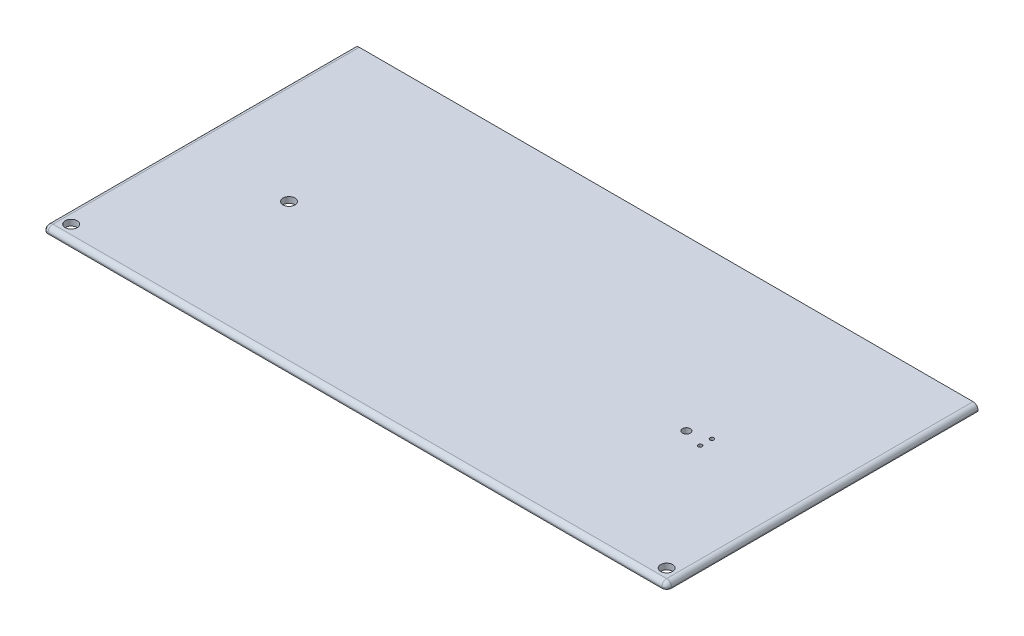
SolidWorks part; units mm, degrees
ref_plane "Front Plane" through (0, 0, 0) normal (0, 0, 1) x (1, 0, 0)
ref_plane "Top Plane" through (0, 0, 0) normal (0, 1, 0) x (1, 0, 0)
ref_plane "Right Plane" through (0, 0, 0) normal (1, 0, 0) x (0, 0, -1)
sketch "Sketch1" plane through (0, 0, 0) normal (0, 1, 0) x (1, 0, 0)
  line L0 (79.25, -36) -> (79.25, 36)
  line L1 (-78, -34.75) -> (78, -34.75)
  line L2 (-78, -34.75) -> (-78, 34.75)
  line L3 (-78, 34.75) -> (78, 34.75)
  line L4 (78, -34.75) -> (78, 34.75)
  line L5 (-78, -34.75) -> (78, 34.75) construction
  line L6 (-78, 34.75) -> (78, -34.75) construction
  line L7 (-79.25, 36) -> (79.25, 36)
  line L8 (-79.25, -36) -> (-79.25, 36)
  line L9 (-78, -36) -> (78, -36)
  line L10 (-78, -36) -> (-78, -86)
  line L11 (-78, -36) -> (78, -36)
  line L12 (-79.25, -36) -> (-79.25, -86)
  line L13 (-79.25, -86) -> (-79.25, -159)
  line L14 (79.25, -36) -> (79.25, -86)
  line L15 (78, -36) -> (78, -86)
  line L16 (-79.25, -36) -> (79.25, -36) construction
  line L17 (-78, -86) -> (-78, -100.5886)
  line L18 (79.25, -86) -> (79.25, -159)
  line L19 (78, -86) -> (78, -157.75)
  line L20 (79.25, -159) -> (-79.25, -159)
  line L21 (78, -159) -> (79.25, -159)
  line L22 (-78, -100.5886) -> (-78, -157.75)
  line L23 (-78, -157.75) -> (78, -157.75)
  line L24 (-78, -157.75) -> (78, -157.75) construction
  line L25 (0, -157.75) -> (0, -117.25)
  line L26 (-40, -117.25) -> (40, -117.25)
  line L27 (-34, -117.25) -> (34, -117.25)
  line L28 (-40, -117.25) -> (-34, -117.25) construction
  circle A0 centre (-37, -117.25) radius 3
  point P0 (0, 0)
  point P27 (0, -117.25)
  point P30 (0, -117.25)
  dimension "D1" = 156
  dimension "D2" = 69.5
  dimension "D4" = 50
  dimension "D5" = 195
  dimension "D6" = 1.25
  dimension "D7" = 40.5
  dimension "D8" = 80
  dimension "D9" = 68
  dimension "D3" = 1.25
sketch "Sketch2" plane through (0, 0, 0) normal (0, 1, 0) x (1, 0, 0)
  line L0 (-79.25, 36) -> (79.25, 36)
  line L1 (79.25, 36) -> (79.25, -159)
  line L2 (79.25, -159) -> (-79.25, -159)
  line L3 (-79.25, -159) -> (-79.25, 36)
extrude "Boss-Extrude1" add sketch "Sketch2" against normal blind 1.25
extrude "Boss-Extrude2" add sketch "Sketch1" along normal blind 105 contours L20 L18 L14 L0 L7 L8 L12 L13 L23 L22 L17 L10 L9 L15 L19 L4 L1 L2 L3 region at (78.9987, 0, 61)
sketch "Sketch4" plane through (0, 0, 0) normal (0, 1, 0) x (1, 0, 0)
  line L0 (-78, -157.75) -> (78, -157.75) construction
  line L1 (0, -157.75) -> (0, -117.75)
  line L2 (0, -5.0875) -> (0, 5.0875) construction
  line L3 (-34, -117.75) -> (34, -117.75)
  line L4 (-40.15, -117.75) -> (-39.575, -117.75)
  line L5 (-40.15, -117.75) -> (-39.575, -117.75) construction
  line L6 (34, -117.75) -> (34.575, -117.75) construction
  line L7 (-34.575, -117.75) -> (34.575, -117.75)
  line L8 (-34.575, -117.75) -> (-34, -117.75) construction
  line L9 (39.575, -117.75) -> (40.15, -117.75) construction
  line L10 (39.575, -117.75) -> (40.15, -117.75)
  circle A0 centre (-37.075, -117.75) radius 2.5
  circle A1 centre (37.075, -117.75) radius 2.5
  point P12 (0, -117.75)
  point P15 (0, -117.75)
  dimension "D1" = 40
  dimension "D2" = 68
  dimension "D3" = 80.3
extrude "Boss-Extrude3" add sketch "Sketch4" along normal blind 8 contours A0 | A1 region at (37.075, 0, 117.75) region at (-37.075, 0, 117.75)
fillet "Fillet2" radius 2 18 edges at (-78, 0, 0) (0, 0, -34.75) (78, 0, 0) (0, 0, 34.75) (0, 0, 36) (78, 0, 96.875) (0, 0, 157.75) (-78, 0, 96.875) (-37.075, 0, 115.25) (37.075, 0, 115.25) (78, 52.5, -34.75) (-78, 52.5, -34.75) (78, 52.5, 34.75) (-78, 52.5, 34.75) (-78, 52.5, 157.75) (78, 52.5, 157.75) (78, 52.5, 36) (-78, 52.5, 36)
sketch "Sketch5" plane through (0, 0, 36) normal (0, 0, 1) x (1, 0, 0)
  line L0 (-76, 105) -> (76, 105) construction
  line L2 (-76, 105) -> (-76, 2) construction
  line L3 (-58.75, 4.5) -> (58.75, 4.5)
  line L4 (-58.75, 4.5) -> (-58.75, 101.5)
  line L5 (-58.75, 101.5) -> (58.75, 101.5)
  line L6 (58.75, 4.5) -> (58.75, 101.5)
  line L7 (-58.75, 53) -> (58.75, 53)
  line L8 (-53.75, 101.5) -> (-53.75, 98)
  line L14 (-58.75, 98) -> (-53.75, 98)
  line L15 (0, 53) -> (0, 77.907)
  circle A0 centre (-53.75, 98) radius 1.55
  circle A1 centre (-53.75, 8) radius 1.55
  circle A2 centre (53.75, 8) radius 1.55
  circle A3 centre (53.75, 98) radius 1.55
  point P8 (0, 53.5)
  dimension "D1" = 97
  dimension "D2" = 117.5
  dimension "D3" = 17.25
  dimension "D4" = 3.5
  dimension "D5" = 5
  dimension "D6" = 3.5
extrude "Cut-Extrude1" cut sketch "Sketch5" against normal blind 8 contours L14 A0 L8 | L8 A0 L14 | A3 | A1 | A2 region at (-54.4078, 98.6578, 36) region at (-53.5307, 97.7807, 36) region at (-53.75, 8, 36) region at (53.75, 98, 36)
sketch "Sketch6" plane through (0, 0, 157.75) normal (0, 0, -1) x (-1, 0, 0)
  line L0 (-76, 2) -> (76, 2) construction
  line L1 (0, 2) -> (0, 22)
  line L2 (0, 5.0875) -> (0, -5.0875) construction
  circle A0 centre (0, 22) radius 8.25
  dimension "D1" = 20
extrude "Cut-Extrude2" cut sketch "Sketch6" against normal blind 8 contours A0 region at (-5.6686, 16.3314, 157.75)
sketch "Sketch8" plane through (-79.25, 0, 0) normal (-1, 0, 0) x (0, 0, 1)
  line L0 (159, 55) -> (116.5, 55)
  line L1 (159, -1.25) -> (159, 105) construction
  line L2 (116.5, 5) -> (116.5, 105)
  line L3 (159, 105) -> (-36, 105) construction
  line L4 (116.5, 55) -> (101.5, 55)
  line L5 (116.5, 55) -> (131.5, 55)
  line L7 (113, 58) -> (120, 58)
  line L8 (113, 58) -> (113, 72)
  line L9 (113, 72) -> (120, 72)
  line L10 (120, 58) -> (120, 72)
  line L11 (113, 58) -> (120, 72) construction
  line L12 (113, 72) -> (120, 58) construction
  circle A0 centre (101.5, 55) radius 3
  circle A1 centre (101.5, 65) radius 3
  circle A2 centre (101.5, 75) radius 3
  circle A3 centre (101.5, 85) radius 3
  circle A4 centre (131.5, 55) radius 3.75
  circle A5 centre (131.5, 75) radius 3.75
  point P9 (116.5, 55)
  point P13 (116.5, 65)
  dimension "D4" = 4
  dimension "D5" = 2
  dimension "D1" = 42.5
  dimension "D2" = 15
  dimension "D3" = 15
  dimension "D6" = 7
  dimension "D7" = 14
  dimension "D8" = 10
  dimension "D9" = 50
extrude "Cut-Extrude3" cut sketch "Sketch8" against normal blind 8 contours A0 | A2 | A3 | A1 | A5 | L8 L9 L10 L7 | A4 region at (-79.25, 55, 98.5849) region at (-79.25, 65, 101.5) region at (-79.25, 75, 101.5) region at (-79.25, 85, 101.5) region at (-79.25, 75, 131.5)
fillet "Fillet3" radius 1.25 4 edges at (0, -1.25, 159) (79.25, -1.25, 61.5) (0, -1.25, -36) (-79.25, -1.25, 61.5)
fillet "Fillet4" radius 1.25 8 edges at (-78.8839, -0.8839, 158.6339) (78.8839, -0.8839, 158.6339) (78.8839, -0.8839, -35.6339) (-78.8839, -0.8839, -35.6339) (-79.25, 52.5, 159) (79.25, 52.5, 159) (79.25, 52.5, -36) (-79.25, 52.5, -36)
sketch "Sketch11" plane through (79.25, 0, 0) normal (1, 0, 0) x (0, 0, -1)
  line L0 (-157.75, 105) -> (34.75, 0) construction
  line L1 (34.75, 105) -> (-157.75, 0)
  line L2 (87.175, 0) -> (-87.175, 0) construction
  line L4 (-111.5, 102.5) -> (-11.5, 102.5)
  line L5 (-111.5, 102.5) -> (-111.5, 2.5)
  line L6 (-111.5, 2.5) -> (-11.5, 2.5)
  line L7 (-11.5, 102.5) -> (-11.5, 2.5)
  line L8 (-111.5, 102.5) -> (-11.5, 2.5) construction
  line L9 (-111.5, 2.5) -> (-11.5, 102.5) construction
  line L10 (-99, 15) -> (-24, 15)
  line L11 (-99, 15) -> (-99, 90)
  line L12 (-99, 90) -> (-24, 90)
  line L13 (-24, 15) -> (-24, 90)
  line L14 (-99, 15) -> (-24, 90) construction
  line L15 (-99, 90) -> (-24, 15) construction
  circle A0 centre (-11.5, 102.5) radius 1.55
  circle A1 centre (-111.5, 102.5) radius 1.55
  circle A2 centre (-99, 90) radius 1.55
  circle A3 centre (-24, 90) radius 1.55
  circle A4 centre (-99, 15) radius 1.55
  circle A5 centre (-111.5, 2.5) radius 1.55
  circle A6 centre (-11.5, 2.5) radius 1.55
  circle A7 centre (-24, 15) radius 1.55
  point P9 (-61.5, 52.5)
  point P14 (-61.5, 52.5)
  dimension "D1" = 100
  dimension "D2" = 100
  dimension "D3" = 75
  dimension "D4" = 75
extrude "Cut-Extrude4" cut sketch "Sketch11" against normal blind 8 contours L7 A0 L4 | L4 A0 L7 | L13 A3 L12 | L12 A3 L13 | L6 A6 L7 | L5 A5 L6 | L6 A5 L5 | L11 A4 L10 | L10 A4 L11 | L10 A7 L13 | L13 A7 L10 | A1 | A2 | A6 region at (79.25, 101.8422, 12.1578) region at (79.25, 102.7193, 11.2807) region at (79.25, 2.2807, 11.2807) region at (79.25, 14.7807, 23.7807) region at (79.25, 15.6578, 24.6578) region at (79.25, 89.3422, 24.6578) region at (79.25, 90.2193, 23.7807) region at (79.25, 15.6578, 98.3422) region at (79.25, 14.7807, 99.2193) region at (79.25, 2.2807, 111.7193) region at (79.25, 3.1578, 110.8422)
sketch "Sketch12" plane through (0, 105, 0) normal (0, 1, 0) x (1, 0, 0)
  line L0 (0, -155.75) -> (0, -144.3132)
  line L1 (-78, -157.75) -> (-73, -157.75)
  line L2 (-78, -157.75) -> (-78, -152.75)
  line L3 (-78, -152.75) -> (-73, -152.75)
  line L4 (-73, -157.75) -> (-73, -152.75)
  line L5 (-76, -155.75) -> (76, -155.75) construction
  line L6 (0, -5.0875) -> (0, 5.0875) construction
  line L7 (78, -152.75) -> (73, -152.75)
  line L8 (73, -157.75) -> (73, -152.75)
  line L9 (78, -157.75) -> (73, -157.75)
  line L10 (78, -157.75) -> (78, -152.75)
  line M6 (76, -157.75) -> (-76, -157.75)
  arc M7 (-76, -157.75) -> (-78, -155.75) centre (-76, -155.75) cw
  line M8 (-78, -155.75) -> (-78, -38)
  line M12 (78, -38) -> (78, -155.75)
  arc M13 (78, -155.75) -> (76, -157.75) centre (76, -155.75) cw
  dimension "D1" = 5
  dimension "D2" = 5
extrude "Boss-Extrude5" add sketch "Sketch12" against normal up to surface (105 mm away) contours L8 L7 M6 M13 M12 | L4 L3 M6 M8 M7 region at (75.427, 105, 155.177) region at (-75.427, 105, 155.177) up to face at (0, 0, 96.875)
fillet "Fillet5" radius 1.25 14 edges at (78, 53.5, 152.75) (77.4142, 0.5858, 152.75) (74.5, 0, 152.75) (73, 0, 154.25) (73, 0.5858, 157.1642) (-73, 0, 154.25) (-73, 0.5858, 157.1642) (-74.5, 0, 152.75) (-77.4142, 0.5858, 152.75) (73, 53.5, 157.75) (73, 52.5, 152.75) (-73, 53.5, 157.75) (-78, 53.5, 152.75) (-73, 52.5, 152.75)
sketch "Sketch14" plane through (0, 105, 0) normal (0, 1, 0) x (1, 0, 0)
  line L0 (78, -38) -> (78, -151.5) construction
  line L1 (73.3661, -153.1161) -> (78, -153.1161)
  line L2 (73.3661, -153.1161) -> (73.3661, -157.75)
  line L3 (73.3661, -157.75) -> (78, -157.75)
  line L4 (78, -153.1161) -> (78, -157.75)
  line L5 (73.3661, -153.1161) -> (78, -157.75) construction
  line L6 (78, -157.75) -> (78.0536, -157.7607) construction
  line L7 (0, -157.75) -> (0, -147.0716)
  line L8 (-71.75, -157.75) -> (71.75, -157.75) construction
  line L9 (0, -58.4375) -> (0, 58.4375) construction
  arc A0 (74.25, -152.75) -> (73, -154) centre (74.25, -154) ccw construction
  circle A1 centre (75.6831, -155.4331) radius 1.525
  circle A2 centre (-75.6831, -155.4331) radius 1.525
extrude "Cut-Extrude5" cut sketch "Sketch14" against normal blind 8 contours A1 | A2 region at (75.6831, 105, 155.4331) region at (-75.6831, 105, 155.4331)
sketch "Sketch15" plane through (0, 105, 0) normal (0, 1, 0) x (1, 0, 0)
  line L16 (76, 33) -> (-76, 33)
  line L17 (-76.25, 32.75) -> (-76.25, -32.75)
  line L18 (-76, -33) -> (76, -33)
  line L19 (76.25, -32.75) -> (76.25, 32.75)
  line L20 (-77.5, 32.75) -> (-77.5, -32.75)
  line L21 (-76, -34.25) -> (76, -34.25)
  line L22 (77.5, -32.75) -> (77.5, 32.75)
  line L23 (76, 34.25) -> (-76, 34.25)
  line L24 (-77.5, 32.75) -> (-77.5, -32.75)
  line L25 (-76, -34.25) -> (76, -34.25)
  line L26 (77.5, -32.75) -> (77.5, 32.75)
  line L27 (76, 34.25) -> (-76, 34.25)
  arc A8 (78, 32.75) -> (76, 34.75) centre (76, 32.75) ccw construction
  arc A17 (-76, 33) -> (-76.25, 32.75) centre (-76, 32.75) ccw
  arc A18 (-76.25, -32.75) -> (-76, -33) centre (-76, -32.75) ccw
  arc A19 (76, -33) -> (76.25, -32.75) centre (76, -32.75) ccw
  arc A20 (76.25, 32.75) -> (76, 33) centre (76, 32.75) ccw
  arc A21 (-76, 34.25) -> (-77.5, 32.75) centre (-76, 32.75) ccw
  arc A22 (-77.5, -32.75) -> (-76, -34.25) centre (-76, -32.75) ccw
  arc A23 (76, -34.25) -> (77.5, -32.75) centre (76, -32.75) ccw
  arc A24 (77.5, 32.75) -> (76, 34.25) centre (76, 32.75) ccw
  arc A25 (-76, 34.25) -> (-77.5, 32.75) centre (-76, 32.75) ccw
  arc A26 (-77.5, -32.75) -> (-76, -34.25) centre (-76, -32.75) ccw
  arc A27 (76, -34.25) -> (77.5, -32.75) centre (76, -32.75) ccw
  arc A28 (77.5, 32.75) -> (76, 34.25) centre (76, 32.75) ccw
  dimension "D1" = 0.5
  dimension "D2" = 1.25
extrude "Boss-Extrude6" add sketch "Sketch15" against normal blind 5 separate body
sketch "Sketch19" plane through (0, 105, 0) normal (0, 1, 0) x (1, 0, 0)
  circle A2 centre (75.6831, -155.4331) radius 1.525
  circle A3 centre (75.6831, -155.4331) radius 1.525
  circle A5 centre (-75.6831, -155.4331) radius 1.525
  circle A6 centre (-75.6831, -155.4331) radius 1.525
  dimension "D1" = 0
  dimension "D2" = 0
extrude "Cut-Extrude10" cut sketch "Sketch19" along normal blind 176.5 and the other way blind 9
sketch "Sketch16" plane through (0, 105, 0) normal (0, 1, 0) x (1, 0, 0)
  line L8 (-79.25, 34.75) -> (-79.25, -157.75)
  line L9 (-78, -159) -> (78, -159)
  line L10 (79.25, -157.75) -> (79.25, 34.75)
  line L11 (78, 36) -> (-78, 36)
  line L12 (-79.25, 34.75) -> (-79.25, -157.75)
  line L13 (-78, -159) -> (78, -159)
  line L14 (79.25, -157.75) -> (79.25, 34.75)
  line L15 (78, 36) -> (-78, 36)
  arc A8 (-79.25, -157.75) -> (-78, -159) centre (-78, -157.75) ccw
  arc A9 (78, -159) -> (79.25, -157.75) centre (78, -157.75) ccw
  arc A10 (79.25, 34.75) -> (78, 36) centre (78, 34.75) ccw
  arc A11 (-78, 36) -> (-79.25, 34.75) centre (-78, 34.75) ccw
  arc A12 (-79.25, -157.75) -> (-78, -159) centre (-78, -157.75) ccw
  arc A13 (78, -159) -> (79.25, -157.75) centre (78, -157.75) ccw
  arc A14 (79.25, 34.75) -> (78, 36) centre (78, 34.75) ccw
  arc A15 (-78, 36) -> (-79.25, 34.75) centre (-78, 34.75) ccw
  dimension "D1" = 0
extrude "Boss-Extrude7" add sketch "Sketch16" along normal blind 1.5
sketch "Sketch17" plane through (0, 105, 0) normal (0, -1, 0) x (1, 0, 0)
  line L5 (97.501, -101.5148) -> (-116.8928, -101.5148)
  line L6 (97.501, -101.5148) -> (97.501, 210.2358)
  line L7 (97.501, 210.2358) -> (-116.8928, 210.2358)
  line L8 (78, -32.75) -> (78, 32.75)
  line L9 (76, 34.75) -> (-76, 34.75)
  line L10 (-78, 32.75) -> (-78, -32.75)
  line L11 (-76, -34.75) -> (76, -34.75)
  line L12 (78, -32.75) -> (78, 32.75)
  line L13 (76, 34.75) -> (-76, 34.75)
  line L14 (-78, 32.75) -> (-78, -32.75)
  line L15 (-76, -34.75) -> (76, -34.75)
  line L16 (-116.8928, -101.5148) -> (-116.8928, 210.2358)
  line L17 (97.501, -101.5148) -> (-116.8928, 210.2358) construction
  line L18 (97.501, 210.2358) -> (-116.8928, -101.5148) construction
  arc A8 (78, 32.75) -> (76, 34.75) centre (76, 32.75) ccw
  arc A9 (-76, 34.75) -> (-78, 32.75) centre (-76, 32.75) ccw
  arc A10 (-78, -32.75) -> (-76, -34.75) centre (-76, -32.75) ccw
  arc A11 (76, -34.75) -> (78, -32.75) centre (76, -32.75) ccw
  arc A12 (78, 32.75) -> (76, 34.75) centre (76, 32.75) ccw
  arc A13 (-76, 34.75) -> (-78, 32.75) centre (-76, 32.75) ccw
  arc A14 (-78, -32.75) -> (-76, -34.75) centre (-76, -32.75) ccw
  arc A15 (76, -34.75) -> (78, -32.75) centre (76, -32.75) ccw
  point P2 (-9.6959, 54.3605)
  dimension "D1" = 0
extrude "Cut-Extrude6" cut sketch "Sketch17" along normal blind 142.5
sketch "Sketch18" plane through (0, 100, 0) normal (0, -1, 0) x (1, 0, 0)
  line L1 (-421.9306, -105.0953) -> (421.9306, -105.0953)
  line L2 (-421.9306, -105.0953) -> (-421.9306, 105.0953)
  line L3 (-421.9306, 105.0953) -> (421.9306, 105.0953)
  line L4 (421.9306, -105.0953) -> (421.9306, 105.0953)
  line L5 (-421.9306, -105.0953) -> (421.9306, 105.0953) construction
  line L6 (-421.9306, 105.0953) -> (421.9306, -105.0953) construction
  point P0 (0, 0)
extrude "Cut-Extrude7" cut sketch "Sketch18" along normal blind 211.5
fillet "Fillet6" radius 1.25 8 edges at (0, 106.5, -36) (78.8839, 106.5, -35.6339) (79.25, 106.5, 61.5) (78.8839, 106.5, 158.6339) (0, 106.5, 159) (-78.8839, 106.5, 158.6339) (-79.25, 106.5, 61.5) (-78.8839, 106.5, -35.6339)
sketch "Sketch21" plane through (0, 106.5, 0) normal (0, 1, 0) x (1, 0, 0)
  line L0 (-78.8839, -158.6339) -> (-75.6807, -155.4307)
  line L1 (0, -159) -> (0, -145.5027)
  line L2 (78, -159) -> (-78, -159) construction
  line L3 (0, -3.575) -> (0, 3.575) construction
  arc A0 (-79.25, -157.75) -> (-78, -159) centre (-78, -157.75) ccw construction
  circle A1 centre (-75.6807, -155.4307) radius 1.525
  circle A2 centre (75.6807, -155.4307) radius 1.525
  dimension "D1" = 4.53
extrude "Cut-Extrude11" cut sketch "Sketch21" against normal blind 46.5 contours A1 | A2
sketch "Sketch22" plane through (0, 106.5, 0) normal (0, 1, 0) x (1, 0, 0)
  line L0 (53, -122.75) -> (-53, -122.75)
  line L1 (-78, -157.75) -> (-53, -157.75)
  line L2 (-78, -157.75) -> (-78, -122.75)
  line L3 (-78, -122.75) -> (-53, -122.75)
  line L4 (-53, -157.75) -> (-53, -122.75)
  line L6 (53, -124.25) -> (53, -121.25)
  line L7 (53, -122.75) -> (48, -122.75)
  circle A0 centre (-53, -122.75) radius 1.525
  circle A1 centre (53, -121.25) radius 0.5
  circle A2 centre (53, -124.25) radius 0.5
  circle A3 centre (48, -122.75) radius 1
  point P9 (0, -122.75)
  point P11 (53, -122.75)
  dimension "D3" = 3
  dimension "D4" = 5
  dimension "D1" = 25
  dimension "D2" = 35
extrude "Cut-Extrude12" cut sketch "Sketch22" against normal blind 46.5 contours L3 A0 L4 | L4 A0 L3 | A2 | A1 | L7 A3 L0 | L0 A3 L7 | L4 A0 L0 region at (-52.3528, 106.5, 123.3972) region at (-53, 106.5, 122.1028) region at (48, 106.5, 123.1744) region at (48, 106.5, 122.3256) region at (53.3436, 106.5, 123.9064) region at (52.6564, 106.5, 120.9064) region at (-53.6472, 106.5, 123.3972)
sketch "Sketch23" plane through (0, 105, 0) normal (0, -1, 0) x (1, 0, 0)
  line L1 (-106.4259, 59.8786) -> (117.9234, 59.8786)
  line L2 (-106.4259, 59.8786) -> (-106.4259, 79.8786)
  line L3 (-106.4259, 79.8786) -> (117.9234, 79.8786)
  line L4 (117.9234, 59.8786) -> (117.9234, 79.8786)
  dimension "D1" = 20
extrude "Cut-Extrude13" cut sketch "Sketch23" against normal blind 108
sketch "Sketch24" plane through (0, 0, 59.8786) normal (0, 0, 1) x (1, 0, 0)
  line L0 (78, 105.25) -> (-78, 105.25) construction
  line L1 (-98.6841, 72.2979) -> (92.8636, 72.2979)
  line L2 (-98.6841, 72.2979) -> (-98.6841, 138.2021)
  line L3 (-98.6841, 138.2021) -> (92.8636, 138.2021)
  line L4 (92.8636, 72.2979) -> (92.8636, 138.2021)
  line L5 (-98.6841, 72.2979) -> (92.8636, 138.2021) construction
  line L6 (-98.6841, 138.2021) -> (92.8636, 72.2979) construction
  point P0 (-2.9102, 105.25)
extrude "Cut-Extrude14" cut sketch "Sketch24" against normal blind 151
